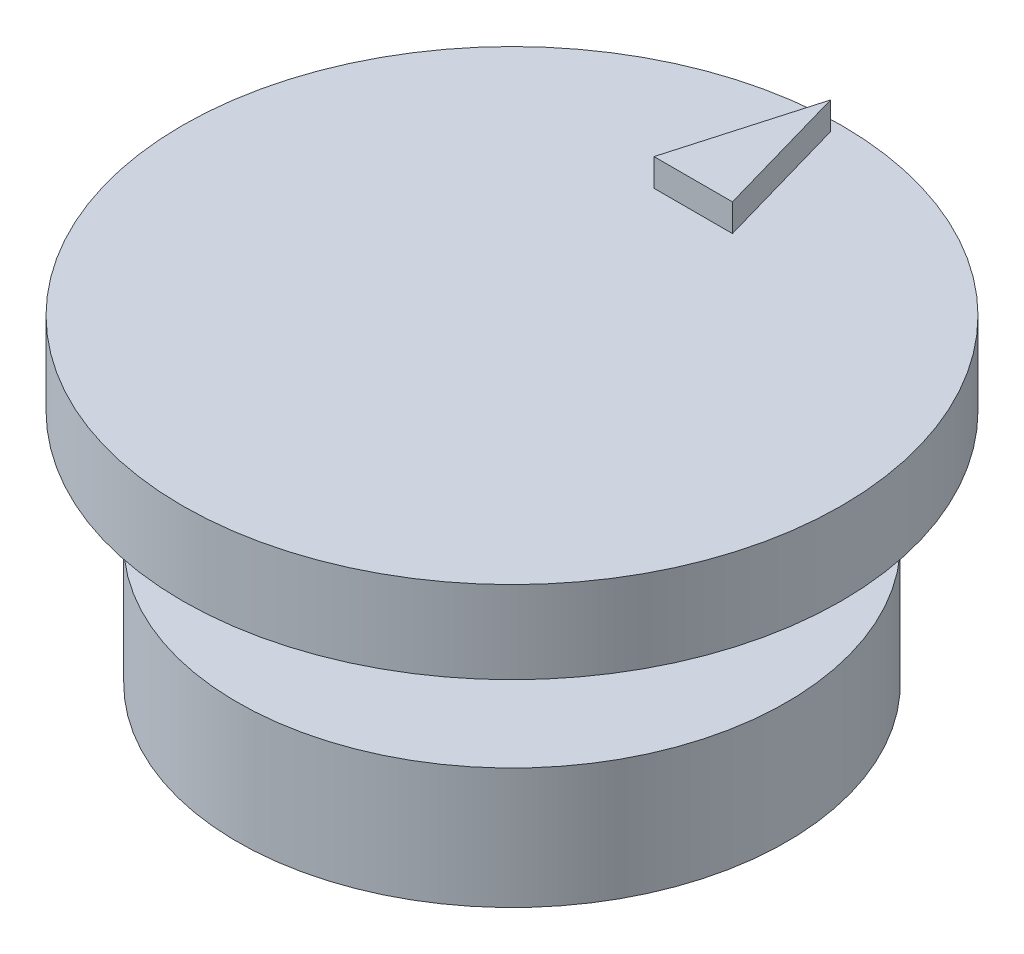
SolidWorks part; units mm, degrees
ref_plane "Front Plane" through (0, 0, 0) normal (0, 0, 1) x (1, 0, 0)
ref_plane "Top Plane" through (0, 0, 0) normal (0, 1, 0) x (1, 0, 0)
ref_plane "Right Plane" through (0, 0, 0) normal (1, 0, 0) x (0, 0, -1)
sketch "Sketch1" plane through (0, 0, 0) normal (0, 0, 1) x (1, 0, 0)
  line L0 (0, -22.1611) -> (0, -36.8931)
  line L1 (0, -36.8931) -> (12.7, -36.8931)
  line L2 (12.7, -36.8931) -> (12.7, -31.3051)
  line L3 (12.7, -31.3051) -> (3.175, -31.3051)
  line L4 (3.175, -31.3051) -> (3.175, -27.4951)
  line L5 (3.175, -27.4951) -> (12.7, -27.4951)
  line L6 (12.7, -27.4951) -> (12.7, -25.9711)
  line L7 (12.7, -25.9711) -> (15.24, -25.9711)
  line L8 (15.24, -25.9711) -> (15.24, -22.1611)
  line L9 (15.24, -22.1611) -> (0, -22.1611)
  dimension "D1" = 3.175
  dimension "D2" = 9.525
  dimension "D3" = 3.81
  dimension "D4" = 5.588
  dimension "D5" = 1.524
  dimension "D6" = 3.81
  dimension "D7" = 12.7
  dimension "D8" = 15.24
revolve "dial base shape" add sketch "Sketch1" angle 360 about L0
sketch "Sketch2" plane through (0, -22.1611, 0) normal (0, 1, 0) x (1, 0, 0)
  line L0 (0, 14.732) -> (-1.8139, 8.382)
  line L1 (-1.8139, 8.382) -> (1.8139, 8.382)
  line L2 (1.8139, 8.382) -> (0, 14.732)
  dimension "D1" = 6.35
  dimension "D2" = 8.382
  dimension "D3" = 6.604
  dimension "D4" = 6.604
extrude "arrow" add sketch "Sketch2" along normal blind 1.27
sketch "Sketch3" plane through (0, -36.8931, 0) normal (0, -1, 0) x (1, 0, 0)
  circle A0 centre (0, -9.8549) radius 1.7989
extrude "flag" add sketch "Sketch3" along normal blind 6.35
